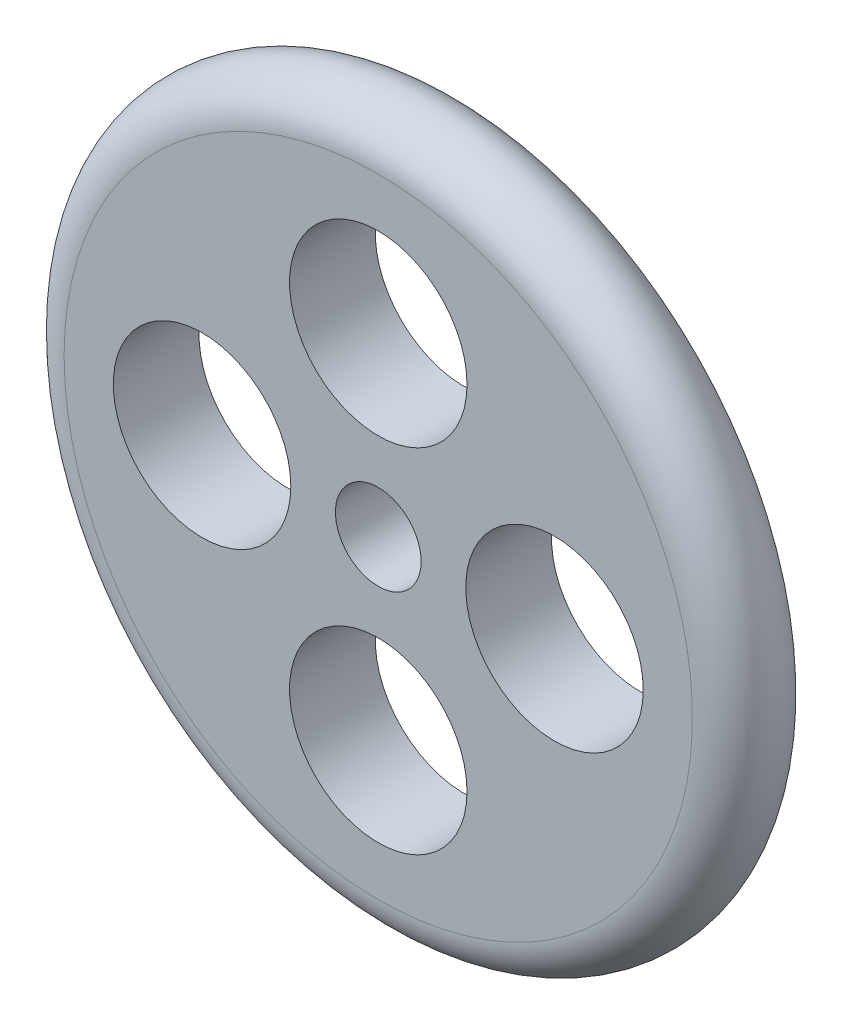
SolidWorks part; units mm, degrees
ref_plane "Front Plane" through (0, 0, 0) normal (0, 0, 1) x (1, 0, 0)
ref_plane "Top Plane" through (0, 0, 0) normal (0, 1, 0) x (1, 0, 0)
ref_plane "Right Plane" through (0, 0, 0) normal (1, 0, 0) x (0, 0, -1)
sketch "Sketch6" plane through (0, 0, 0) normal (0, 1, 0) x (1, 0, 0)
  line L0 (0, 75.7869) -> (110, 75.7869)
  line L1 (0, 75.7869) -> (0, 45.7869)
  line L2 (0, 45.7869) -> (110, 45.7869)
  arc A0 (110, 45.7869) -> (110, 75.7869) centre (110, 60.7869) ccw
revolve "Revolve3" add sketch "Sketch6" angle 360 about L1
sketch "Sketch10" plane through (0, 0, -45.7869) normal (0, 0, 1) x (1, 0, 0)
  circle A0 centre (0, 0) radius 15
  dimension "D1" = 30
extrude "Cut-Extrude1" cut sketch "Sketch10" against normal through all contours A0
sketch "Sketch11" plane through (0, 0, -45.7869) normal (0, 0, 1) x (1, 0, 0)
  line L0 (0, -16.5) -> (0, 16.5) construction
  circle A0 centre (0, 61.7011) radius 31.0725
  circle A1 centre (61.7011, 0) radius 31.0725
  circle A2 centre (0, -61.7011) radius 31.0725
  circle A3 centre (-61.7011, 0) radius 31.0725
  point P13 (0, 0)
  dimension "D1" = 4
extrude "Cut-Extrude2" cut sketch "Sketch11" against normal through all
